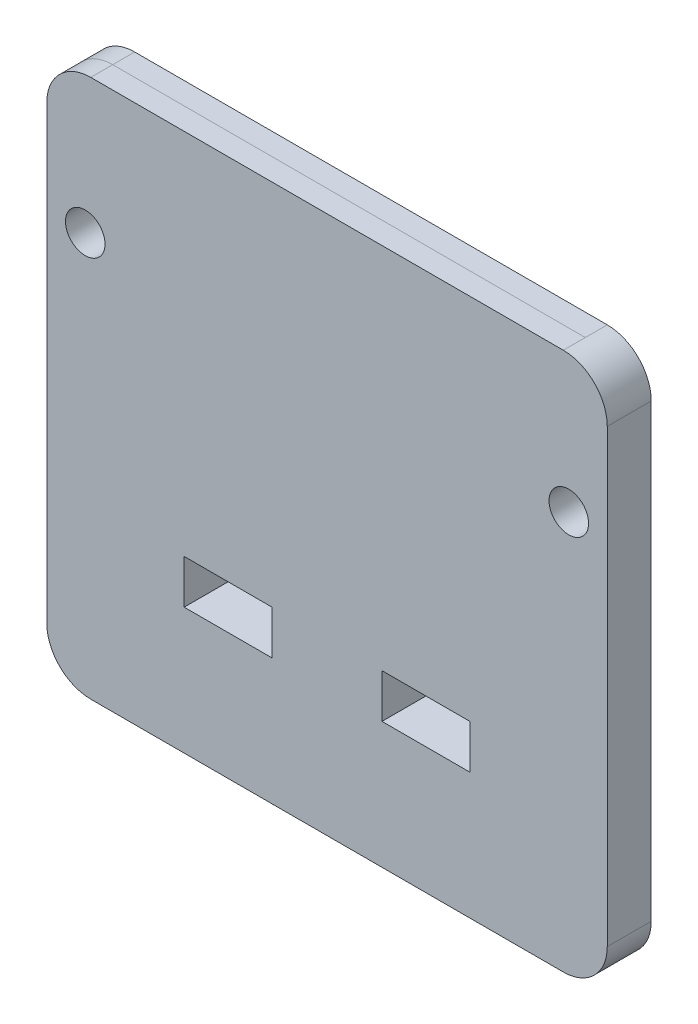
SolidWorks part; units mm, degrees
material "Pink Foam"
ref_plane "Front Plane" through (0, 0, 0) normal (0, 0, 1) x (1, 0, 0)
ref_plane "Top Plane" through (0, 0, 0) normal (0, 1, 0) x (1, 0, 0)
ref_plane "Right Plane" through (0, 0, 0) normal (1, 0, 0) x (0, 0, -1)
sketch "Sketch1" plane through (0, 0, 0) normal (0, 0, 1) x (1, 0, 0)
  line L1 (-139.7, -203.2) -> (139.7, -203.2) construction
  line L2 (-165.1, -177.8) -> (-165.1, 177.8) construction
  line L3 (-139.7, 203.2) -> (139.7, 203.2) construction
  line L4 (165.1, -177.8) -> (165.1, 177.8) construction
  line L5 (-165.1, -203.2) -> (165.1, 203.2) construction
  line L6 (-165.1, 203.2) -> (165.1, -203.2) construction
  line L7 (-136.525, -155.575) -> (136.525, -155.575)
  line L8 (-161.925, -130.175) -> (-161.925, 130.175)
  line L9 (-136.525, 155.575) -> (136.525, 155.575)
  line L10 (161.925, -130.175) -> (161.925, 130.175)
  line L11 (-161.925, -155.575) -> (161.925, 155.575) construction
  line L12 (-161.925, 155.575) -> (161.925, -155.575) construction
  arc A0 (-139.7, -203.2) -> (-165.1, -177.8) centre (-139.7, -177.8) cw construction
  arc A1 (139.7, -203.2) -> (165.1, -177.8) centre (139.7, -177.8) ccw construction
  arc A2 (139.7, 203.2) -> (165.1, 177.8) centre (139.7, 177.8) cw construction
  arc A3 (-165.1, 177.8) -> (-139.7, 203.2) centre (-139.7, 177.8) cw construction
  circle A4 centre (-139.7, 76.2) radius 11.422
  circle A5 centre (139.7, 76.2) radius 11.422
  arc A6 (-136.525, -155.575) -> (-161.925, -130.175) centre (-136.525, -130.175) cw
  arc A7 (136.525, -155.575) -> (161.925, -130.175) centre (136.525, -130.175) ccw
  arc A8 (136.525, 155.575) -> (161.925, 130.175) centre (136.525, 130.175) cw
  arc A9 (-161.925, 130.175) -> (-136.525, 155.575) centre (-136.525, 130.175) cw
  point P0 (0, 0)
  point P23 (0, 0)
  dimension "D3" = 25.4
  dimension "D7" = 22.844
  dimension "D8" = 323.85
  dimension "D10" = 25.4
  dimension "D1" = 330.2
  dimension "D2" = 406.4
  dimension "D4" = 25.4
  dimension "D5" = 127
  dimension "D6" = 25.4
  dimension "D9" = 311.15
extrude "Boss-Extrude1" add sketch "Sketch1" along normal blind 25.4
ref_plane "Plane1" through (0, 0, 12.7) normal (0, 0, 1) x (1, 0, 0)
sketch "Sketch2" plane through (0, 0, 0) normal (0, 0, -1) x (-1, 0, 0)
  line L8 (-82.55, -82.55) -> (-31.75, -82.55)
  line L9 (-31.75, -82.55) -> (-31.75, -57.15)
  line L10 (-31.75, -57.15) -> (-82.55, -57.15)
  line L11 (-82.55, -57.15) -> (-82.55, -82.55)
  line L16 (31.75, -82.55) -> (82.55, -82.55)
  line L17 (31.75, -57.15) -> (31.75, -82.55)
  line L18 (82.55, -57.15) -> (31.75, -57.15)
  line L19 (82.55, -82.55) -> (82.55, -57.15)
  dimension "D1" = 31.75
  dimension "D2" = 82.55
  dimension "D3" = 31.75
  dimension "D4" = 57.15
  dimension "D5" = 82.55
extrude "Foam Insert Cut-Throughs" cut sketch "Sketch2" against normal blind 25.4
split line "Split Line1"
